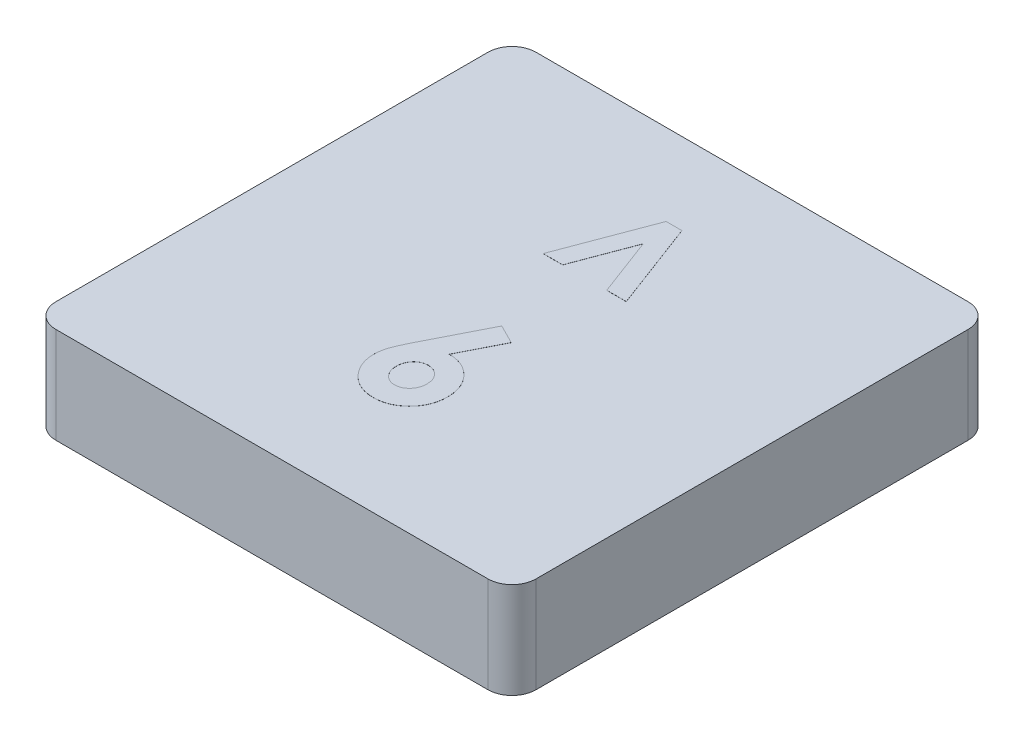
SolidWorks part; units mm, degrees
ref_plane "Front Plane" through (0, 0, 0) normal (0, 0, 1) x (1, 0, 0)
ref_plane "Top Plane" through (0, 0, 0) normal (0, 1, 0) x (1, 0, 0)
ref_plane "Right Plane" through (0, 0, 0) normal (1, 0, 0) x (0, 0, -1)
sketch "Sketch1" plane through (0, 0, 0) normal (0, 1, 0) x (1, 0, 0)
  line L0 (0, 0) -> (12.7, 0)
  line L1 (12.7, 0) -> (12.7, 12.7)
  line L2 (12.7, 12.7) -> (0, 12.7)
  line L3 (0, 12.7) -> (0, 0)
  dimension "D1" = 12.7
  dimension "D2" = 12.7
extrude "Boss-Extrude1" add sketch "Sketch1" along normal blind 2.54
fillet "Fillet1" radius 0.635 4 edges at (0, 1.27, -12.7) (12.7, 1.27, -12.7) (12.7, 1.27, 0) (0, 1.27, 0)
shell "Shell1" thickness 0.635 removed face at (6.35, 0, -6.35)
sketch "Sketch2" plane through (0, 1.905, 0) normal (0, -1, 0) x (-1, 0, 0)
  line L0 (-0.635, 6.35) -> (-12.065, 6.35) construction
  line L1 (-0.635, 12.065) -> (-0.635, 0.635) construction
  line L2 (-12.065, 0.635) -> (-12.065, 12.065) construction
  line L3 (-6.35, 0.635) -> (-6.35, 12.065) construction
  line L4 (-0.635, 0.635) -> (-12.065, 0.635) construction
  line L5 (-12.065, 12.065) -> (-0.635, 12.065) construction
  circle A0 centre (-6.35, 6.35) radius 2.54
  dimension "D1" = 5.08
extrude "Boss-Extrude2" add sketch "Sketch2" along normal up to surface (1.905 mm away) up to face at (6.35, 0, -6.35)
sketch "Sketch4" plane through (0, 2.54, 0) normal (0, 1, 0) x (1, 0, 0)
  line L0 (0, 12.065) -> (0, 0.635) construction
  line L1 (12.065, 12.7) -> (0.635, 12.7) construction
  line L2 (0.635, 0) -> (12.065, 0) construction
  text T0 "<b>6</b>"
  text T1 "<b>^</b>"
  dimension "D1" = 5.08
  dimension "D2" = 5.207
  dimension "D3" = 5.334
  dimension "D4" = 2.7178
extrude "Boss-Extrude4" add sketch "Sketch4" along normal blind 0.0025
